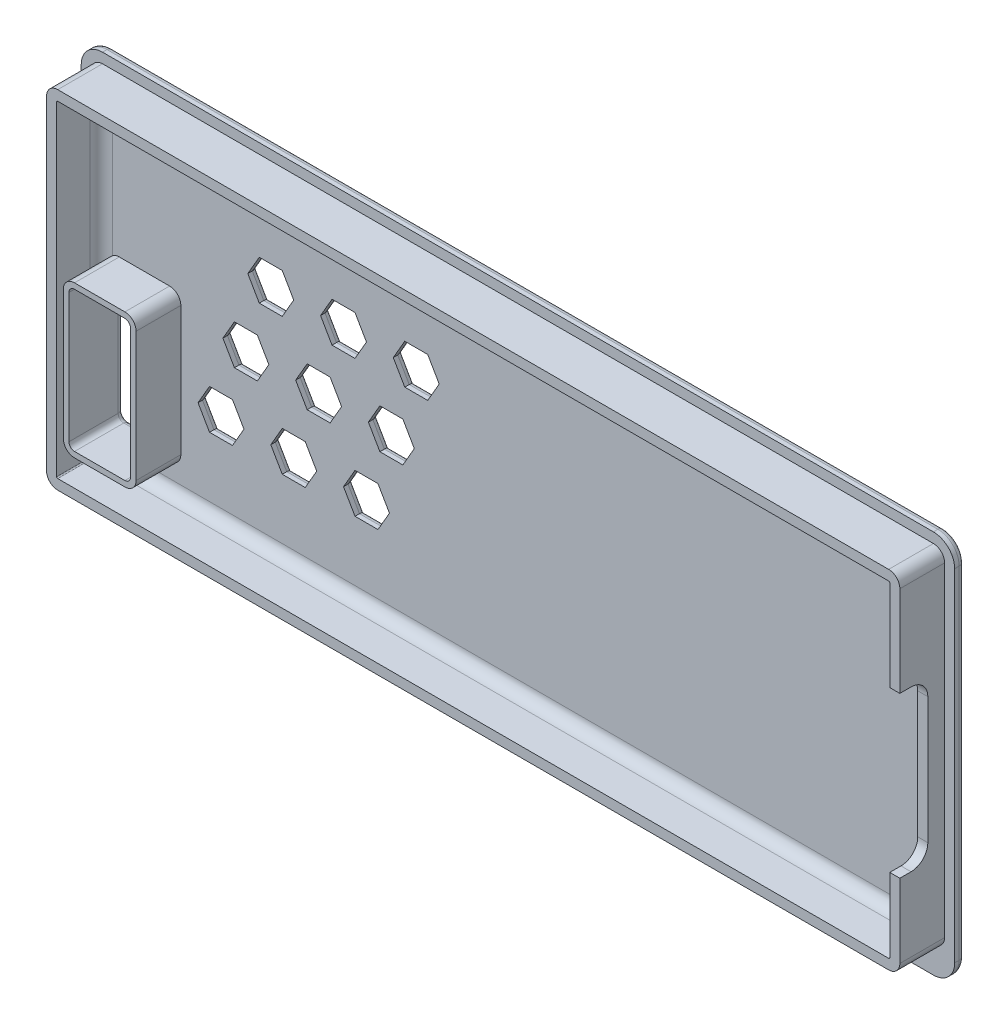
SolidWorks part; units mm, degrees
ref_plane "Front Plane" through (0, 0, 0) normal (0, 0, 1) x (1, 0, 0)
ref_plane "Top Plane" through (0, 0, 0) normal (0, 1, 0) x (1, 0, 0)
ref_plane "Right Plane" through (0, 0, 0) normal (1, 0, 0) x (0, 0, -1)
sketch "Sketch1" plane through (0, 0, 0) normal (0, 0, 1) x (1, 0, 0)
  line L1 (0, 0) -> (156.1, 0)
  line L2 (0, 0) -> (0, 68.6)
  line L3 (0, 68.6) -> (156.1, 68.6)
  line L4 (156.1, 0) -> (156.1, 68.6)
  dimension "D1" = 156.1
  dimension "D2" = 68.6
extrude "Boss-Extrude1" add sketch "Sketch1" along normal blind 1.8
sketch "Sketch2" plane through (0, 0, 1.8) normal (0, 0, 1) x (1, 0, 0)
  line L0 (1.8, 66.8) -> (1.8, 4.8)
  line L1 (3.6, 65) -> (152.5, 65)
  line L2 (3.6, 65) -> (3.6, 6.6)
  line L3 (3.6, 6.6) -> (152.5, 6.6)
  line L4 (152.5, 65) -> (152.5, 6.6)
  line L5 (1.8, 4.8) -> (154.3, 4.8)
  line L6 (154.3, 66.8) -> (154.3, 4.8)
  line L7 (1.8, 66.8) -> (154.3, 66.8)
  line L8 (0, 68.6) -> (0, 0) construction
  line L9 (156.1, 68.6) -> (0, 68.6) construction
  line L10 (0, 0) -> (156.1, 0) construction
  line L11 (156.1, 0) -> (156.1, 68.6) construction
  dimension "D2" = 1.8
  dimension "D3" = 1.8
  dimension "D4" = 4.8
  dimension "D5" = 1.8
  dimension "D1" = 1.8
extrude "Boss-Extrude2" add sketch "Sketch2" along normal blind 8
fillet "Fillet1" radius 2 4 edges at (1.8, 66.8, 5.8) (1.8, 4.8, 5.8) (154.3, 4.8, 5.8) (154.3, 66.8, 5.8)
fillet "Fillet3" radius 0.2 4 edges at (3.6, 6.6, 5.8) (3.6, 65, 5.8) (152.5, 6.6, 5.8) (152.5, 65, 5.8)
fillet "Fillet4" radius 3.8 4 edges at (0, 68.6, 0.9) (156.1, 68.6, 0.9) (156.1, 0, 0.9) (0, 0, 0.9)
sketch "Sketch3" plane through (0, 0, 9.8) normal (0, 0, 1) x (1, 0, 0)
  line L0 (152.5, 6.8) -> (152.5, 64.8) construction
  line L1 (152.5, 48.6) -> (154.3, 48.6)
  line L2 (152.5, 48.6) -> (152.5, 20)
  line L3 (152.5, 20) -> (154.3, 20)
  line L4 (154.3, 48.6) -> (154.3, 20)
  line L5 (154.3, 6.8) -> (154.3, 64.8) construction
  line L6 (152.3, 68.6) -> (3.8, 68.6) construction
  line L7 (3.8, 0) -> (152.3, 0) construction
  dimension "D1" = 20
  dimension "D2" = 20
extrude "Cut-Extrude1" cut sketch "Sketch3" against normal blind 5
fillet "Fillet5" radius 3 2 edges at (153.4, 20, 4.8) (153.4, 48.6, 4.8)
sketch "Sketch4" plane through (0, 0, 1.8) normal (0, 0, 1) x (1, 0, 0)
  line L0 (152.3, 68.6) -> (3.8, 68.6) construction
  line L1 (5.8, 37.4) -> (16.8, 37.4)
  line L2 (5.8, 37.4) -> (5.8, 12.3)
  line L3 (5.8, 12.3) -> (16.8, 12.3)
  line L4 (16.8, 37.4) -> (16.8, 12.3)
  line L5 (0, 64.8) -> (0, 3.8) construction
  dimension "D1" = 25.1
  dimension "D2" = 11
  dimension "D3" = 56.3
  dimension "D4" = 16.8
extrude "Cut-Extrude2" cut sketch "Sketch4" against normal blind 5
sketch "Sketch5" plane through (0, 0, 1.8) normal (0, 0, 1) x (1, 0, 0)
  line L0 (4.8, 38.4) -> (17.8, 38.4)
  line L1 (5.8, 37.4) -> (16.8, 37.4)
  line L2 (5.8, 37.4) -> (5.8, 12.3)
  line L3 (5.8, 12.3) -> (16.8, 12.3)
  line L4 (16.8, 37.4) -> (16.8, 12.3)
  line L5 (17.8, 38.4) -> (17.8, 11.3)
  line L6 (4.8, 11.3) -> (17.8, 11.3)
  line L7 (4.8, 38.4) -> (4.8, 11.3)
  dimension "D1" = 1
extrude "Boss-Extrude3" add sketch "Sketch5" along normal blind 8
fillet "Fillet6" radius 1 4 edges at (5.8, 12.3, 4.9) (16.8, 12.3, 4.9) (16.8, 37.4, 4.9) (5.8, 37.4, 4.9)
fillet "Fillet7" radius 2 4 edges at (4.8, 38.4, 5.8) (4.8, 11.3, 5.8) (17.8, 11.3, 5.8) (17.8, 38.4, 5.8)
sketch "Sketch6" plane through (0, 0, 1.8) normal (0, 0, 1) x (1, 0, 0)
  line L0 (50.9764, 47.3157) -> (48.9245, 50.8696)
  line L1 (37.9764, 47.3157) -> (35.9245, 50.8696)
  line L2 (35.9245, 50.8696) -> (31.8207, 50.8696)
  line L3 (31.8207, 50.8696) -> (29.7689, 47.3157)
  line L4 (29.7689, 47.3157) -> (31.8207, 43.7617)
  line L5 (31.8207, 43.7617) -> (35.9245, 43.7617)
  line L6 (35.9245, 43.7617) -> (37.9764, 47.3157)
  line L7 (48.9245, 50.8696) -> (44.8207, 50.8696)
  line L8 (44.8207, 50.8696) -> (42.7689, 47.3157)
  line L9 (42.7689, 47.3157) -> (44.8207, 43.7617)
  line L10 (44.8207, 43.7617) -> (48.9245, 43.7617)
  line L11 (48.9245, 43.7617) -> (50.9764, 47.3157)
  line L12 (63.9764, 47.3157) -> (61.9245, 50.8696)
  line L13 (61.9245, 50.8696) -> (57.8207, 50.8696)
  line L14 (57.8207, 50.8696) -> (55.7689, 47.3157)
  line L15 (55.7689, 47.3157) -> (57.8207, 43.7617)
  line L16 (57.8207, 43.7617) -> (61.9245, 43.7617)
  line L17 (61.9245, 43.7617) -> (63.9764, 47.3157)
  line L18 (46.5301, 35.0997) -> (44.4782, 38.6536)
  line L19 (44.4782, 38.6536) -> (40.3745, 38.6536)
  line L20 (40.3745, 38.6536) -> (38.3226, 35.0997)
  line L21 (38.3226, 35.0997) -> (40.3745, 31.5457)
  line L22 (40.3745, 31.5457) -> (44.4782, 31.5457)
  line L23 (44.4782, 31.5457) -> (46.5301, 35.0997)
  line L24 (59.5301, 35.0997) -> (57.4782, 38.6536)
  line L25 (57.4782, 38.6536) -> (53.3745, 38.6536)
  line L26 (53.3745, 38.6536) -> (51.3226, 35.0997)
  line L27 (51.3226, 35.0997) -> (53.3745, 31.5457)
  line L28 (53.3745, 31.5457) -> (57.4782, 31.5457)
  line L29 (57.4782, 31.5457) -> (59.5301, 35.0997)
  line L30 (42.0838, 22.8837) -> (40.032, 26.4376)
  line L31 (40.032, 26.4376) -> (35.9282, 26.4376)
  line L32 (35.9282, 26.4376) -> (33.8763, 22.8837)
  line L33 (33.8763, 22.8837) -> (35.9282, 19.3297)
  line L34 (35.9282, 19.3297) -> (40.032, 19.3297)
  line L35 (40.032, 19.3297) -> (42.0838, 22.8837)
  line L36 (55.0838, 22.8837) -> (53.032, 26.4376)
  line L37 (53.032, 26.4376) -> (48.9282, 26.4376)
  line L38 (48.9282, 26.4376) -> (46.8763, 22.8837)
  line L39 (46.8763, 22.8837) -> (48.9282, 19.3297)
  line L40 (48.9282, 19.3297) -> (53.032, 19.3297)
  line L41 (53.032, 19.3297) -> (55.0838, 22.8837)
  line L42 (33.5301, 35.0997) -> (31.4782, 38.6536)
  line L43 (31.4782, 38.6536) -> (27.3745, 38.6536)
  line L44 (27.3745, 38.6536) -> (25.3226, 35.0997)
  line L45 (25.3226, 35.0997) -> (27.3745, 31.5457)
  line L46 (27.3745, 31.5457) -> (31.4782, 31.5457)
  line L47 (31.4782, 31.5457) -> (33.5301, 35.0997)
  line L48 (29.0838, 22.8837) -> (27.032, 26.4376)
  line L49 (27.032, 26.4376) -> (22.9282, 26.4376)
  line L50 (22.9282, 26.4376) -> (20.8763, 22.8837)
  line L51 (20.8763, 22.8837) -> (22.9282, 19.3297)
  line L52 (22.9282, 19.3297) -> (27.032, 19.3297)
  line L53 (27.032, 19.3297) -> (29.0838, 22.8837)
  circle A0 centre (33.8726, 47.3157) radius 3.554 construction
  dimension "D1" = 3
  dimension "D2" = 3
extrude "Cut-Extrude3" cut sketch "Sketch6" against normal blind 8
fillet "Fillet8" radius 1 8 edges at (154.987, 67.487, 0) (156.1, 34.3, 0) (154.987, 1.113, 0) (78.05, 0, 0) (1.113, 1.113, 0) (0, 34.3, 0) (1.113, 67.487, 0) (78.05, 68.6, 0)
fillet "Fillet9" radius 1 8 edges at (16.5071, 12.5929, 0) (16.8, 24.85, 0) (16.5071, 37.1071, 0) (11.3, 37.4, 0) (6.0929, 37.1071, 0) (5.8, 24.85, 0) (6.0929, 12.5929, 0) (11.3, 12.3, 0)
fillet "Fillet10" radius 1 54 edges at (24.9801, 19.3297, 0) (21.9023, 21.1067, 0) (21.9023, 24.6606, 0) (24.9801, 26.4376, 0) (28.0579, 24.6606, 0) (28.0579, 21.1067, 0) (37.9801, 19.3297, 0) (41.0579, 21.1067, 0) (34.9023, 21.1067, 0) (34.9023, 24.6606, 0) (37.9801, 26.4376, 0) (41.0579, 24.6606, 0) (47.9023, 24.6606, 0) (47.9023, 21.1067, 0) (50.9801, 19.3297, 0) (54.0579, 21.1067, 0) (54.0579, 24.6606, 0) (50.9801, 26.4376, 0) (32.5042, 33.3227, 0) (29.4263, 31.5457, 0) (26.3485, 33.3227, 0) (26.3485, 36.8766, 0) (29.4263, 38.6536, 0) (32.5042, 36.8766, 0) (39.3485, 36.8766, 0) (39.3485, 33.3227, 0) (42.4263, 31.5457, 0) (45.5042, 33.3227, 0) (45.5042, 36.8766, 0) (42.4263, 38.6536, 0) (52.3485, 36.8766, 0) (52.3485, 33.3227, 0) (55.4263, 31.5457, 0) (58.5042, 33.3227, 0) (58.5042, 36.8766, 0) (55.4263, 38.6536, 0) (33.8726, 43.7617, 0) (30.7948, 45.5387, 0) (30.7948, 49.0927, 0) (33.8726, 50.8696, 0) (36.9504, 49.0927, 0) (36.9504, 45.5387, 0) (43.7948, 45.5387, 0) (43.7948, 49.0927, 0) (46.8726, 50.8696, 0) (49.9504, 49.0927, 0) (49.9504, 45.5387, 0) (46.8726, 43.7617, 0) (62.9504, 45.5387, 0) (59.8726, 43.7617, 0) (56.7948, 45.5387, 0) (56.7948, 49.0927, 0) (59.8726, 50.8696, 0) (62.9504, 49.0927, 0)
fillet "Fillet11" radius 2 8 edges at (152.4414, 64.9414, 1.8) (152.5, 35.8, 1.8) (152.4414, 6.6586, 1.8) (78.05, 6.6, 1.8) (3.6586, 6.6586, 1.8) (3.6, 35.8, 1.8) (3.6586, 64.9414, 1.8) (78.05, 65, 1.8)
